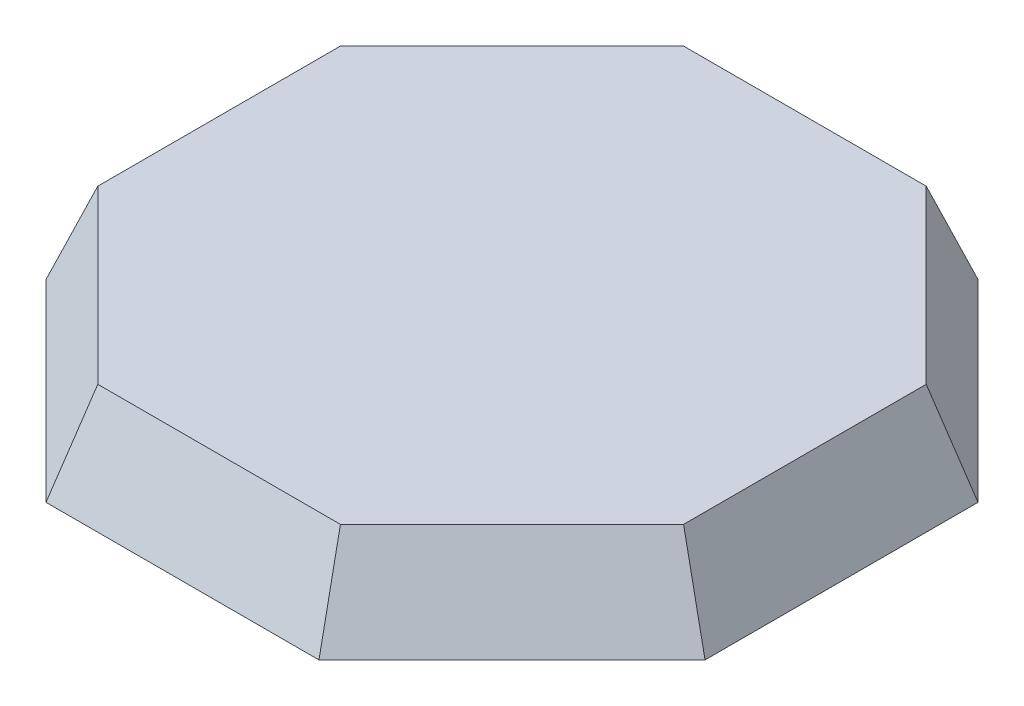
SolidWorks part; units mm, degrees
ref_plane "Front Plane" through (0, 0, 0) normal (0, 0, 1) x (1, 0, 0)
ref_plane "Top Plane" through (0, 0, 0) normal (0, 1, 0) x (1, 0, 0)
ref_plane "Right Plane" through (0, 0, 0) normal (1, 0, 0) x (0, 0, -1)
sketch "Sketch3" plane through (0, 0, 0) normal (0, 1, 0) x (1, 0, 0)
  line L0 (-90, 37.2792) -> (-90, -37.2792)
  line L1 (-90, -37.2792) -> (0, 0)
  line L2 (0, 0) -> (-90, 37.2792)
  dimension "D1" = 45
  dimension "D2" = 74.5584
extrude "Boss-Extrude1" add sketch "Sketch3" along normal blind 25
sketch "Sketch4" plane through (0, 0, 0) normal (0, 0, 1) x (1, 0, 0)
  line L0 (-90, 25) -> (-90, 0)
  line L1 (-90, 25) -> (0, 25) construction
  line L2 (-90, 25) -> (-90, 0) construction
  line L3 (-90, 0) -> (-80, 25)
  line L4 (-80, 25) -> (-90, 25)
  dimension "D1" = 10
extrude "Cut-Extrude1" cut sketch "Sketch4" against normal through all both and the other way through all
pattern_circular "CirPattern1" count 8 every 45 about axis through (0, 25, 0) along (0, -1, 0) of "Cut-Extrude1", "Boss-Extrude1"
shell "Shell2" thickness 10 removed face at (0, 0, 0)
sketch "Sketch5" plane through (0, 15, 0) normal (0, -1, 0) x (1, 0, 0)
  line L1 (-79.2297, -32.818) -> (-79.2297, -26.829)
  line L4 (-32.818, -79.2297) -> (-79.2297, -32.818) construction
  line L6 (-79.2297, -32.818) -> (-73.2297, -30.3327) construction
  line L7 (-77.0928, -28.5771) -> (-78.9802, -31.0367) construction
  line L8 (-78.9802, -31.0367) -> (-77.7937, -33.9011) construction
  line L9 (-77.7937, -33.9011) -> (-74.7199, -34.3058) construction
  line L10 (-74.7199, -34.3058) -> (-72.8325, -31.8461) construction
  line L11 (-72.8325, -31.8461) -> (-74.0189, -28.9817) construction
  line L12 (-74.0189, -28.9817) -> (-77.0928, -28.5771) construction
  line L13 (-79.2297, -32.818) -> (-79.2297, 32.818) construction
  line L14 (-79.2297, -32.818) -> (-74.9948, -37.0529)
  circle A0 centre (-75.9063, -31.4414) radius 2.685 construction
  arc A2 (-74.9948, -37.0529) -> (-79.2297, -26.829) centre (-75.9063, -31.4414) ccw
  point P0 (-73.4257, -30.4139)
  point P26 (-76.2297, -31.5754)
  dimension "D1" = 5.37
  dimension "D2" = 3
  dimension "D3" = 0.35
extrude "Boss-Extrude2" add sketch "Sketch5" along normal up to surface (15 mm away) up to face at (0, 0, 0)
sketch "Sketch8" plane through (0, 0, 0) normal (0, -1, 0) x (1, 0, 0)
  circle A0 centre (-75.9063, -31.4414) radius 1.75
  arc A1 (-74.9948, -37.0529) -> (-79.2297, -26.829) centre (-75.9063, -31.4414) ccw construction
  dimension "D1" = 3.5
extrude "Cut-Extrude3" cut sketch "Sketch8" against normal blind 3.89
sketch "Sketch10" plane through (0, 3.89, 0) normal (0, -1, 0) x (1, 0, 0)
  circle A0 centre (-75.9063, -31.4414) radius 1.5
  dimension "D1" = 3
extrude "Cut-Extrude5" cut sketch "Sketch10" against normal blind 10
ref_axis "Axis1" through (0, 0, 0) along (0, 1, 0)
pattern_circular "CirPattern2" count 8 every 45 about axis through (0, 0, 0) along (0, 1, 0) of "Cut-Extrude3", "Boss-Extrude2", "Cut-Extrude5"
sketch "Sketch11" plane through (0, 15, 0) normal (0, -1, 0) x (1, 0, 0)
  line L0 (39.8413, -58.0501) -> (39.8413, -18.7501) construction
  line L1 (32.8413, -11.7501) -> (-33.1587, -11.7501) construction
  line L2 (-34.3587, -19.0501) -> (34.0413, -58.3501) construction
  line L3 (-34.3587, -58.3501) -> (34.0413, -19.0501) construction
  line L4 (69.0448, -26.4907) -> (68.866, 29.709) construction
  line L5 (51.9366, 45.0097) -> (27.0602, 69.6301) construction
  line L6 (66.8596, 31.7026) -> (44.6597, 31.632) construction
  line L7 (68.766, 29.7087) -> (68.9448, -26.491) construction
  line L9 (15.2424, 57.6894) -> (40.1188, 33.069) construction
  line L10 (27.0602, 69.6301) -> (15.2424, 57.6894) construction
  line L12 (-34.3587, -65.6501) -> (34.0413, -65.6501)
  line L13 (-41.6587, -19.0501) -> (-41.6587, -58.3501)
  line L14 (34.0413, -11.7501) -> (-34.3587, -11.7501)
  line L15 (41.3413, -58.3501) -> (41.3413, -19.0501)
  line L16 (-49.9217, 28.8909) -> (-45.9018, 28.8909)
  line L17 (-45.9018, 28.8909) -> (-45.5576, 30.956)
  line L18 (-45.5576, 30.956) -> (-50.2659, 30.956)
  line L19 (-50.2659, 30.956) -> (-49.9217, 28.8909)
  line L24 (26.6693, 70.017) -> (14.4997, 57.721)
  line L25 (52.3275, 44.6228) -> (26.6693, 70.017)
  line L26 (14.4997, 57.721) -> (40.158, 32.3268)
  line L27 (40.158, 32.3268) -> (52.3275, 44.6228)
  line L29 (-45.8076, 29.456) -> (-45.5576, 30.956)
  line L30 (-45.5576, 30.956) -> (-50.2659, 30.956)
  line L31 (-50.2659, 30.956) -> (-50.0159, 29.456)
  line L36 (45.3949, -29.716) -> (66.6548, -29.6483)
  line L37 (68.9475, -27.341) -> (68.7633, 30.5587)
  line L38 (66.4559, 32.8514) -> (45.1961, 32.7837)
  line L39 (42.9034, 30.4764) -> (43.0876, -27.4233)
  line L40 (-61.6124, 9.3101) -> (-63.4618, 9.0019)
  line L41 (-63.4618, 9.0019) -> (-63.4618, 13.7102)
  line L42 (-63.4618, 13.7102) -> (-61.6124, 13.4019)
  line L43 (-61.9618, 9.2519) -> (-63.4618, 9.0019)
  line L44 (-63.4618, 9.0019) -> (-63.4618, 13.7102)
  line L45 (-63.4618, 13.7102) -> (-61.9618, 13.4602)
  line L129 (8.9125, 34.7615) -> (9.3836, 60.7563)
  line L130 (9.3836, 60.7563) -> (-36.7089, 61.5915)
  line L131 (-36.7089, 61.5915) -> (-37.1799, 35.5968)
  line L132 (-37.1799, 35.5968) -> (8.9125, 34.7615)
  line L169 (-50.0159, 29.456) -> (-61.9618, 29.456)
  line L170 (4.7841, 29.456) -> (-45.8076, 29.456)
  line L172 (9.2424, 30.956) -> (8.94, 29.1416)
  line L173 (4.5341, 30.956) -> (9.2424, 30.956)
  line L174 (4.8365, 29.1416) -> (4.5341, 30.956)
  line L175 (20.9382, 10.356) -> (20.9382, 10.5133)
  line L176 (20.9382, 12.1988) -> (20.9382, 12.356)
  line L177 (-61.9618, 10.5133) -> (-61.9618, 10.356)
  line L178 (-61.9618, 12.356) -> (-61.9618, 12.1988)
  line L179 (-61.9618, 12.1988) -> (-61.9618, 10.5133)
  line L180 (-61.9618, -6.744) -> (20.9382, -6.744)
  line L181 (-61.9618, 10.356) -> (-61.9618, -6.744)
  line L182 (20.9382, -6.744) -> (20.9382, 10.356)
  line L183 (20.9382, 10.5133) -> (20.9382, 12.1988)
  line L184 (20.9382, 12.356) -> (20.9382, 29.456)
  line L185 (20.9382, 29.456) -> (-61.9618, 29.456)
  line L186 (-61.9618, 29.456) -> (-61.9618, 12.356)
  line L187 (20.9382, 10.356) -> (20.9382, 10.5133)
  line L188 (20.9382, 12.1988) -> (20.9382, 12.356)
  line L192 (-61.9618, -6.744) -> (20.9382, -6.744)
  line L193 (-61.9618, 9.2519) -> (-61.9618, -6.744)
  line L194 (20.9382, -6.744) -> (20.9382, 10.356)
  line L195 (20.9382, 10.5133) -> (20.9382, 12.1988)
  line L196 (20.9382, 12.356) -> (20.9382, 29.456)
  line L197 (20.9382, 29.456) -> (8.9924, 29.456)
  line L198 (-61.9618, 29.456) -> (-61.9618, 13.4602)
  line L199 (9.2424, 30.956) -> (8.9924, 29.456)
  line L200 (4.5341, 30.956) -> (9.2424, 30.956)
  line L208 (4.7841, 29.456) -> (4.5341, 30.956)
  arc A12 (34.0413, -65.6501) -> (41.3413, -58.3501) centre (34.0413, -58.3501) ccw
  arc A13 (-41.6587, -58.3501) -> (-34.3587, -65.6501) centre (-34.3587, -58.3501) ccw
  arc A14 (-34.3587, -11.7501) -> (-41.6587, -19.0501) centre (-34.3587, -19.0501) ccw
  arc A15 (41.3413, -19.0501) -> (34.0413, -11.7501) centre (34.0413, -19.0501) ccw
  arc A24 (43.0876, -27.4233) -> (45.3949, -29.716) centre (45.3876, -27.416) ccw
  arc A25 (66.6548, -29.6483) -> (68.9475, -27.341) centre (66.6475, -27.3483) ccw
  arc A26 (68.7633, 30.5587) -> (66.4559, 32.8514) centre (66.4633, 30.5514) ccw
  arc A27 (45.1961, 32.7837) -> (42.9034, 30.4764) centre (45.2034, 30.4837) ccw
  point P13 (-0.1587, -11.7501)
  point P15 (-0.1587, -11.7501)
  point P72 (68.8554, 1.6088)
  point P73 (68.8554, 1.6088)
  point P82 (39.4984, 57.3199)
  point P83 (39.4984, 57.3199)
  dimension "D12" = 7.3
  dimension "D16" = 2.3
  dimension "D4" = 25.999
  dimension "D5" = 46.1
  dimension "D8" = 0.3
  dimension "D13" = 83
  dimension "D14" = 53.9
  dimension "D15" = 25.86
  dimension "D3" = 62.5
  dimension "D17" = 17.3
  dimension "D2" = 36.1
  dimension "D9" = 0.3
  dimension "D10" = 0.3
  dimension "D11" = 0.3
extrude "Cut-Extrude7" cut sketch "Sketch11" against normal blind 2
sketch "Sketch13" plane through (0, 17, 0) normal (0, -1, 0) x (1, 0, 0)
  line L4 (41.3413, -58.3501) -> (41.3413, -19.0501)
  line L5 (34.0413, -11.7501) -> (-34.3587, -11.7501)
  line L6 (-41.6587, -19.0501) -> (-41.6587, -58.3501)
  line L7 (-34.3587, -65.6501) -> (34.0413, -65.6501)
  line L9 (34.0413, -11.7501) -> (-34.3587, -11.7501)
  line L10 (-41.6587, -19.0501) -> (-41.6587, -58.3501)
  line L11 (-34.3587, -65.6501) -> (34.0413, -65.6501)
  line L15 (41.3413, -58.3501) -> (41.3413, -19.0501)
  arc A4 (34.0413, -65.6501) -> (41.3413, -58.3501) centre (34.0413, -58.3501) ccw
  arc A6 (-34.3587, -11.7501) -> (-41.6587, -19.0501) centre (-34.3587, -19.0501) ccw
  arc A7 (-41.6587, -58.3501) -> (-34.3587, -65.6501) centre (-34.3587, -58.3501) ccw
  arc A10 (-34.3587, -11.7501) -> (-41.6587, -19.0501) centre (-34.3587, -19.0501) ccw
  arc A11 (-41.6587, -58.3501) -> (-34.3587, -65.6501) centre (-34.3587, -58.3501) ccw
  arc A14 (34.0413, -65.6501) -> (41.3413, -58.3501) centre (34.0413, -58.3501) ccw
  arc A16 (41.3413, -19.0501) -> (34.0413, -11.7501) centre (34.0413, -19.0501) ccw
  arc A17 (41.3413, -19.0501) -> (34.0413, -11.7501) centre (34.0413, -19.0501) ccw
  dimension "D1" = 0
extrude "Cut-Extrude8" cut sketch "Sketch13" against normal blind 3.7
fillet "Fillet1" radius 1 4 edges at (9.3836, 16, 60.7563) (-36.7089, 16, 61.5915) (8.9125, 16, 34.7615) (-37.1799, 16, 35.5968)
sketch "Sketch14" plane through (0, 17, 0) normal (0, -1, 0) x (1, 0, 0)
  line L4 (45.3949, -29.716) -> (66.6548, -29.6483)
  line L5 (68.9475, -27.341) -> (68.7633, 30.5587)
  line L6 (66.4559, 32.8514) -> (45.1961, 32.7837)
  line L7 (42.9034, 30.4764) -> (43.0876, -27.4233)
  line L8 (45.3949, -29.716) -> (66.6548, -29.6483)
  line L9 (68.9475, -27.341) -> (68.7633, 30.5587)
  line L10 (66.4559, 32.8514) -> (45.1961, 32.7837)
  line L11 (42.9034, 30.4764) -> (43.0876, -27.4233)
  line L12 (52.3275, 44.6228) -> (26.6693, 70.017)
  line L13 (26.6693, 70.017) -> (14.4997, 57.721)
  line L14 (14.4997, 57.721) -> (40.158, 32.3268)
  line L15 (40.158, 32.3268) -> (52.3275, 44.6228)
  line L16 (52.3275, 44.6228) -> (26.6693, 70.017)
  line L17 (26.6693, 70.017) -> (14.4997, 57.721)
  line L18 (14.4997, 57.721) -> (40.158, 32.3268)
  line L19 (40.158, 32.3268) -> (52.3275, 44.6228)
  arc A4 (43.0876, -27.4233) -> (45.3949, -29.716) centre (45.3876, -27.416) ccw
  arc A5 (66.6548, -29.6483) -> (68.9475, -27.341) centre (66.6475, -27.3483) ccw
  arc A6 (68.7633, 30.5587) -> (66.4559, 32.8514) centre (66.4633, 30.5514) ccw
  arc A7 (45.1961, 32.7837) -> (42.9034, 30.4764) centre (45.2034, 30.4837) ccw
  arc A8 (43.0876, -27.4233) -> (45.3949, -29.716) centre (45.3876, -27.416) ccw
  arc A9 (66.6548, -29.6483) -> (68.9475, -27.341) centre (66.6475, -27.3483) ccw
  arc A10 (68.7633, 30.5587) -> (66.4559, 32.8514) centre (66.4633, 30.5514) ccw
  arc A11 (45.1961, 32.7837) -> (42.9034, 30.4764) centre (45.2034, 30.4837) ccw
  dimension "D1" = 0
  dimension "D2" = 0
extrude "Cut-Extrude9" cut sketch "Sketch14" against normal blind 1
sketch "Sketch15" plane through (0, 18, 0) normal (0, -1, 0) x (1, 0, 0)
  line L0 (66.4559, 32.8514) -> (45.1961, 32.7837) construction
  line L1 (68.9475, -27.341) -> (68.7633, 30.5587) construction
  arc A54 (64.6141, 29.1948) -> (64.6142, 29.1945) centre (65.6161, 29.6487) ccw
  arc A55 (64.6142, 29.1945) -> (64.6141, 29.1948) centre (65.6161, 29.6487) ccw
  dimension "D1" = 1.1
  dimension "D2" = 1.1
  dimension "D3" = 3.2
  dimension "D4" = 3.15
extrude "Cut-Extrude11" cut sketch "Sketch15" against normal blind 4
ref_plane "Plane1" through (-0.0044, 0, 1.3897) normal (0.0032, 0, -1) x (-1, 0, -0.0032)
ref_plane "Plane2" through (55.9299, 0, 0.178) normal (-1, 0, -0.0032) x (-0.0032, 0, 1)
mirror "Mirror1" about plane through (-0.0044, 0, 1.3897) normal (0.0032, 0, -1) of "Cut-Extrude11"
mirror "Mirror2" about plane through (55.9299, 0, 0.178) normal (-1, 0, -0.0032) of "Mirror1"
sketch "Sketch16" plane through (0, 17, 0) normal (0, -1, 0) x (1, 0, 0)
  line L16 (4.7841, 29.456) -> (-45.8076, 29.456)
  line L17 (-45.8076, 29.456) -> (-45.5576, 30.956)
  line L18 (-45.5576, 30.956) -> (-50.2659, 30.956)
  line L19 (-50.2659, 30.956) -> (-50.0159, 29.456)
  line L20 (-50.0159, 29.456) -> (-61.9618, 29.456)
  line L21 (-61.9618, 29.456) -> (-61.9618, 13.4602)
  line L22 (-61.9618, 13.4602) -> (-63.4618, 13.7102)
  line L23 (-63.4618, 13.7102) -> (-63.4618, 9.0019)
  line L24 (-63.4618, 9.0019) -> (-61.9618, 9.2519)
  line L25 (-61.9618, 9.2519) -> (-61.9618, -6.744)
  line L26 (-61.9618, -6.744) -> (20.9382, -6.744)
  line L27 (20.9382, -6.744) -> (20.9382, 29.456)
  line L28 (20.9382, 29.456) -> (8.9924, 29.456)
  line L29 (8.9924, 29.456) -> (9.2424, 30.956)
  line L30 (9.2424, 30.956) -> (4.5341, 30.956)
  line L31 (4.5341, 30.956) -> (4.7841, 29.456)
  line L32 (4.7841, 29.456) -> (-45.8076, 29.456)
  line L33 (-45.8076, 29.456) -> (-45.5576, 30.956)
  line L34 (-45.5576, 30.956) -> (-50.2659, 30.956)
  line L35 (-50.2659, 30.956) -> (-50.0159, 29.456)
  line L36 (-50.0159, 29.456) -> (-61.9618, 29.456)
  line L37 (-61.9618, 29.456) -> (-61.9618, 13.4602)
  line L38 (-61.9618, 13.4602) -> (-63.4618, 13.7102)
  line L39 (-63.4618, 13.7102) -> (-63.4618, 9.0019)
  line L40 (-63.4618, 9.0019) -> (-61.9618, 9.2519)
  line L41 (-61.9618, 9.2519) -> (-61.9618, -6.744)
  line L42 (-61.9618, -6.744) -> (20.9382, -6.744)
  line L43 (20.9382, -6.744) -> (20.9382, 29.456)
  line L44 (20.9382, 29.456) -> (8.9924, 29.456)
  line L45 (8.9924, 29.456) -> (9.2424, 30.956)
  line L46 (9.2424, 30.956) -> (4.5341, 30.956)
  line L47 (4.5341, 30.956) -> (4.7841, 29.456)
  dimension "D1" = 0
extrude "Cut-Extrude12" cut sketch "Sketch16" against normal blind 2.5
sketch "Sketch17" plane through (0, 18, 0) normal (0, -1, 0) x (1, 0, 0)
  line L0 (26.6693, 70.017) -> (14.4997, 57.721) construction
  line L1 (14.4997, 57.721) -> (40.158, 32.3268) construction
  line L2 (27.3289, 45.0239) -> (39.4984, 57.3199) construction
  line L3 (52.3275, 44.6228) -> (26.6693, 70.017) construction
  circle A0 centre (18.3891, 57.6704) radius 1
  circle A2 centre (40.0672, 36.2154) radius 1
  dimension "D1" = 2.8
  dimension "D3" = 2
  dimension "D2" = 2.7
extrude "Cut-Extrude13" cut sketch "Sketch17" against normal blind 4
sketch "Sketch18" plane through (0, 17, 0) normal (0, -1, 0) x (1, 0, 0)
  line L4 (8.9306, 35.7614) -> (9.3654, 59.7564)
  line L5 (8.3837, 60.7744) -> (-35.709, 61.5734)
  line L6 (-36.727, 60.5917) -> (-37.1618, 36.5966)
  line L7 (-36.1801, 35.5787) -> (7.9127, 34.7797)
  line L8 (8.9306, 35.7614) -> (9.3654, 59.7564)
  line L9 (8.3837, 60.7744) -> (-35.709, 61.5734)
  line L10 (-36.727, 60.5917) -> (-37.1618, 36.5966)
  line L11 (-36.1801, 35.5787) -> (7.9127, 34.7797)
  arc A4 (9.3654, 59.7564) -> (8.3837, 60.7744) centre (8.3656, 59.7745) ccw
  arc A5 (-35.709, 61.5734) -> (-36.727, 60.5917) centre (-35.7272, 60.5735) ccw
  arc A6 (-37.1618, 36.5966) -> (-36.1801, 35.5787) centre (-36.162, 36.5785) ccw
  arc A7 (7.9127, 34.7797) -> (8.9306, 35.7614) centre (7.9308, 35.7795) ccw
  arc A8 (9.3654, 59.7564) -> (8.3837, 60.7744) centre (8.3656, 59.7745) ccw
  arc A9 (-35.709, 61.5734) -> (-36.727, 60.5917) centre (-35.7272, 60.5735) ccw
  arc A10 (-37.1618, 36.5966) -> (-36.1801, 35.5787) centre (-36.162, 36.5785) ccw
  arc A11 (7.9127, 34.7797) -> (8.9306, 35.7614) centre (7.9308, 35.7795) ccw
  dimension "D1" = 0
extrude "Cut-Extrude14" cut sketch "Sketch18" against normal blind 0.5
sketch "Sketch19" plane through (0, 0, 0) normal (0, -1, 0) x (1, 0, 0)
  line L0 (56.0238, -56.0238) -> (63.6396, -63.6396) construction
  line L1 (74.9948, -37.0529) -> (37.0529, -74.9948) construction
  line L2 (90, -37.2792) -> (37.2792, -90) construction
  circle A0 centre (52.7607, -66.9028) radius 3.8
  circle A1 centre (66.9028, -52.7607) radius 3.8
  dimension "D1" = 7.6
  dimension "D3" = 5.3852
  dimension "D2" = 10
extrude "Cut-Extrude15" cut sketch "Sketch19" against normal blind 3
pattern_circular "CirPattern3" count 8 every 45 about axis through (0, 0, 0) along (0, 1, 0) skipping 3, 7 of "Cut-Extrude15"
